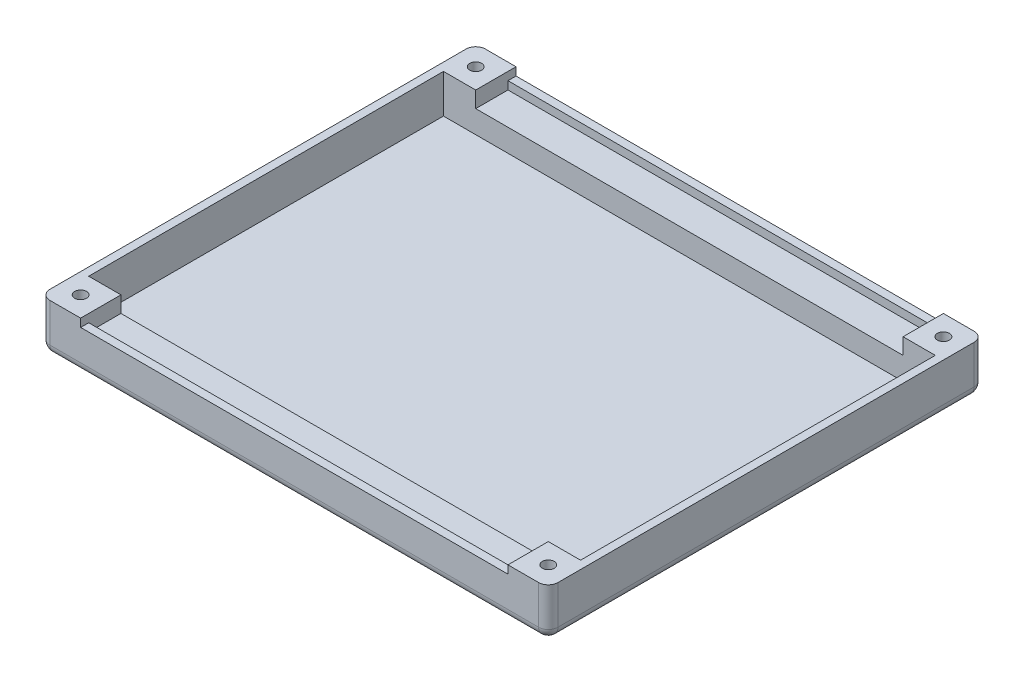
SolidWorks part; units mm, degrees
ref_plane "Front Plane" through (0, 0, 0) normal (0, 0, 1) x (1, 0, 0)
ref_plane "Top Plane" through (0, 0, 0) normal (0, 1, 0) x (1, 0, 0)
ref_plane "Right Plane" through (0, 0, 0) normal (1, 0, 0) x (0, 0, -1)
sketch "Sketch1" plane through (0, 0, 0) normal (0, 1, 0) x (1, 0, 0)
  line L1 (-100.0125, -85.725) -> (100.0125, -85.725)
  line L2 (-100.0125, -85.725) -> (-100.0125, 85.725)
  line L3 (-100.0125, 85.725) -> (100.0125, 85.725)
  line L4 (100.0125, -85.725) -> (100.0125, 85.725)
  line L5 (-100.0125, -85.725) -> (100.0125, 85.725) construction
  line L6 (-100.0125, 85.725) -> (100.0125, -85.725) construction
  point P0 (0, 0)
  dimension "D1" = 200.025
  dimension "D2" = 171.45
extrude "Boss-Extrude1" add sketch "Sketch1" along normal blind 19.05
sketch "Sketch2" plane through (0, 19.05, 0) normal (0, 1, 0) x (1, 0, 0)
  line L0 (100.0125, -85.725) -> (100.0125, 85.725) construction
  line L1 (-96.8375, -69.85) -> (96.8375, -69.85)
  line L2 (-96.8375, -69.85) -> (-96.8375, 69.85)
  line L3 (-96.8375, 69.85) -> (96.8375, 69.85)
  line L4 (96.8375, -69.85) -> (96.8375, 69.85)
  line L5 (-96.8375, -69.85) -> (96.8375, 69.85) construction
  line L6 (-96.8375, 69.85) -> (96.8375, -69.85) construction
  line L7 (-100.0125, -85.725) -> (100.0125, -85.725) construction
  point P0 (0, 0)
  dimension "D1" = 3.175
  dimension "D2" = 15.875
extrude "Cut-Extrude1" cut sketch "Sketch2" against normal offset from surface (15.24 mm away) 3.81 up to face at (0, 0, 0)
sketch "Sketch4" plane through (0, 19.05, 0) normal (0, 1, 0) x (1, 0, 0)
  line L8 (100.0125, 85.725) -> (-100.0125, 85.725) construction
  line L9 (-84.1375, -85.725) -> (84.1375, -85.725)
  line L10 (-84.1375, -85.725) -> (-84.1375, 85.725)
  line L11 (-84.1375, 85.725) -> (84.1375, 85.725)
  line L12 (84.1375, -85.725) -> (84.1375, 85.725)
  line L13 (-84.1375, -85.725) -> (84.1375, 85.725) construction
  line L14 (-84.1375, 85.725) -> (84.1375, -85.725) construction
  line L15 (100.0125, -85.725) -> (100.0125, 85.725) construction
  point P0 (0, 0)
  dimension "D1" = 15.875
extrude "Cut-Extrude2" cut sketch "Sketch4" against normal blind 3.175
sketch "Sketch5" plane through (0, 15.875, 0) normal (0, 1, 0) x (1, 0, 0)
  line L0 (-96.8375, -69.85) -> (96.8375, -69.85) construction
  line L1 (-84.1375, -69.85) -> (84.1375, -69.85)
  line L2 (-84.1375, -69.85) -> (-84.1375, -82.55)
  line L3 (-84.1375, -82.55) -> (84.1375, -82.55)
  line L4 (84.1375, -69.85) -> (84.1375, -82.55)
  line L6 (-84.1375, -69.85) -> (-84.1375, -85.725) construction
  line L7 (84.1375, -85.725) -> (84.1375, -69.85) construction
  dimension "D1" = 12.7
extrude "Cut-Extrude3" cut sketch "Sketch5" against normal blind 3.175
sketch "Sketch7" plane through (0, 15.875, 0) normal (0, 1, 0) x (1, 0, 0)
  line L1 (-84.1375, 82.55) -> (84.1375, 82.55)
  line L2 (-84.1375, 82.55) -> (-84.1375, 69.85)
  line L3 (-84.1375, 69.85) -> (84.1375, 69.85)
  line L4 (84.1375, 82.55) -> (84.1375, 69.85)
  line L5 (-84.1375, 85.725) -> (-84.1375, 69.85) construction
  line L6 (84.1375, 69.85) -> (-84.1375, 69.85) construction
  line L7 (84.1375, 69.85) -> (84.1375, 85.725) construction
  dimension "D1" = 12.7
extrude "Cut-Extrude5" cut sketch "Sketch7" against normal blind 3.175
sketch "Sketch11" plane through (0, 19.05, 0) normal (0, 1, 0) x (1, 0, 0)
  line L0 (100.0125, 85.725) -> (84.1375, 85.725) construction
  line L3 (92.075, 77.7875) -> (84.1375, 77.7875) construction
  line L9 (84.1375, 69.85) -> (84.1375, 85.725) construction
  line L10 (0, 0) -> (96.8375, 0) construction
  line L11 (96.8375, -69.85) -> (96.8375, 69.85) construction
  line L12 (92.075, -77.7875) -> (84.1375, -77.7875) construction
  circle A2 centre (92.075, 77.7875) radius 2.3495
  circle A4 centre (92.075, -77.7875) radius 2.3495
  point P1 (110.31, 95.31)
  point P4 (92.075, 85.725)
  dimension "D1" = 4.699
extrude "Cut-Extrude6" cut sketch "Sketch11" against normal blind 33.5
fillet "Fillet3" radius 3.81 8 edges at (-100.0125, 9.525, 85.725) (0, 0, 85.725) (100.0125, 9.525, 85.725) (100.0125, 0, 0) (100.0125, 9.525, -85.725) (0, 0, -85.725) (-100.0125, 9.525, -85.725) (-100.0125, 0, 0)
mirror "Mirror1" about plane through (0, 0, 0) normal (1, 0, 0) of "Cut-Extrude6"
